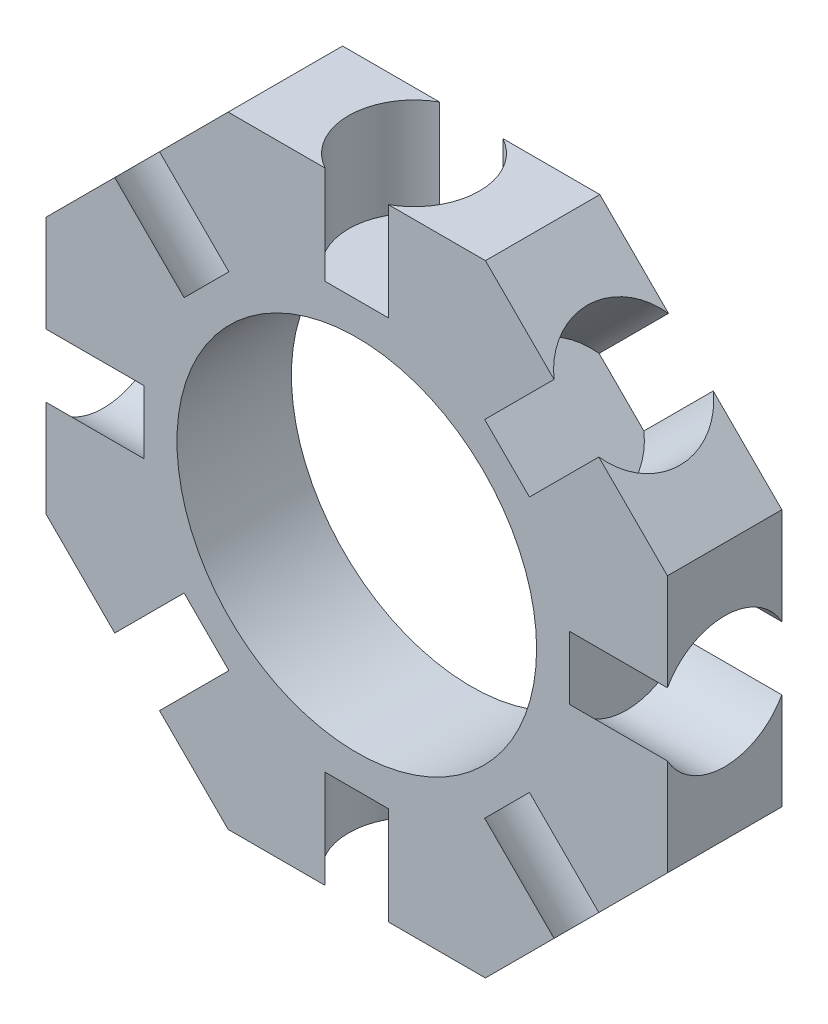
SolidWorks part; units mm, degrees
ref_plane "Top Plane" through (0, 0, 0) normal (0, 0, 1) x (1, 0, 0)
ref_plane "Right Plane" through (0, 0, 0) normal (0, 1, 0) x (1, 0, 0)
ref_plane "Front Plane" through (0, 0, 0) normal (1, 0, 0) x (0, 0, -1)
ref_axis "x-axis" through (-88.99, 0, 0) along (1, 0, 0)
ref_axis "y-axis" through (0, -55, 0) along (0, 1, 0)
ref_axis "z-axis" through (0, 0, 55) along (0, 0, -1)
sketch "Sketch1" plane through (0, 0, 0) normal (0, 0, 1) x (1, 0, 0)
  line L0 (7.8701, 19) -> (-7.8701, 19)
  line L1 (-19, 7.8701) -> (-19, -7.8701)
  line L2 (-19, -7.8701) -> (-7.8701, -19)
  line L3 (-7.8701, -19) -> (7.8701, -19)
  line L4 (7.8701, -19) -> (19, -7.8701)
  line L5 (19, -7.8701) -> (19, 7.8701)
  line L6 (19, 7.8701) -> (7.8701, 19)
  line L7 (-7.8701, 19) -> (-19, 7.8701)
  line L8 (-19, 0) -> (0, 0) construction
  circle A0 centre (0, 0) radius 11
  circle A1 centre (0, 0) radius 19 construction
  circle A2 centre (0, 0) radius 20.5655 construction
  dimension "D1" = 22
  dimension "D2" = 8
extrude "Boss-Extrude1" add sketch "Sketch1" along normal mid plane 7
sketch "Sketch2" plane through (0, -19, 0) normal (0, -1, 0) x (-1, 0, 0)
  circle A0 centre (0, 0) radius 4
  dimension "D1" = 8
extrude "Cut-Extrude3" cut sketch "Sketch2" against normal blind 6
pattern_circular "CirPattern1" count 8 over 360 about axis through (0, 0, 3.5) along (0, 0, 1) of "Cut-Extrude3"
